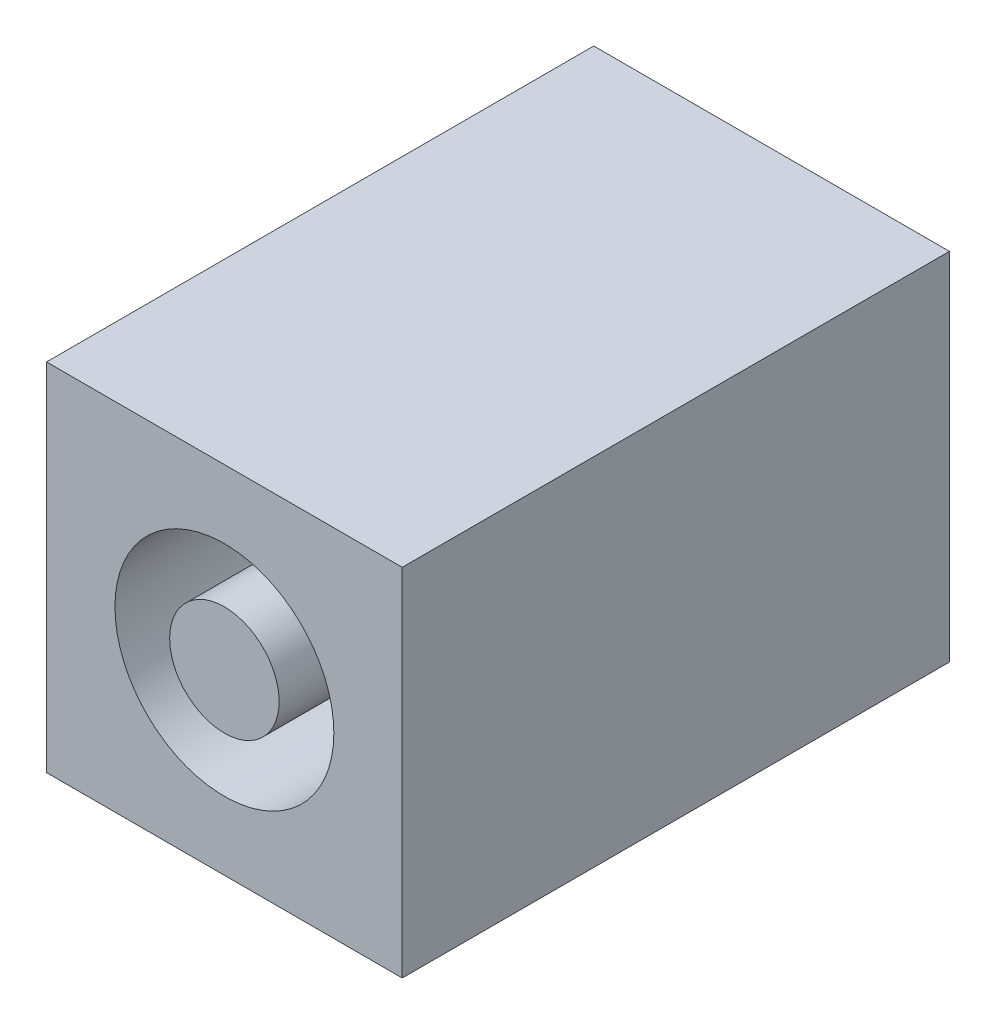
SolidWorks part; units mm, degrees
ref_plane "정면" through (0, 0, 0) normal (0, 0, 1) x (1, 0, 0)
ref_plane "윗면" through (0, 0, 0) normal (0, 1, 0) x (1, 0, 0)
ref_plane "우측면" through (0, 0, 0) normal (1, 0, 0) x (0, 0, -1)
ref_axis "기준축2" through (0, 0, 210) along (0, 0, -1)
ref_axis "기준축4" through (0, 55, 0) along (0, -1, 0)
sketch "스케치1" plane through (0, 0, 0) normal (0, 0, 1) x (1, 0, 0)
  line L1 (-65, 65) -> (65, 65)
  line L2 (-65, 65) -> (-65, -65)
  line L3 (-65, -65) -> (65, -65)
  line L4 (65, 65) -> (65, -65)
  circle A0 centre (0, 0) radius 35 construction
  circle A1 centre (0, 0) radius 25 construction
  circle A2 centre (0, 0) radius 40
  circle A3 centre (0, 0) radius 20
  point P11 (65, 0)
  point P14 (0, 65)
  dimension "D1" = 70
  dimension "D2" = 10
  dimension "D5" = 5
  dimension "D6" = 5
  dimension "D3" = 130
  dimension "D4" = 130
extrude "보스-돌출1" add sketch "스케치1" along normal blind 200 contours L4 L1 L2 L3 A2 | A3 region at (0, 63.1615, 0) region at (0, 0, 0)
sketch "스케치2" plane through (0, 0, 0) normal (0, 0, -1) x (-1, 0, 0)
  line L1 (-65, 65) -> (65, 65)
  line L2 (-65, 65) -> (-65, -65)
  line L3 (-65, -65) -> (65, -65)
  line L4 (65, 65) -> (65, -65)
extrude "보스-돌출2" add sketch "스케치2" against normal blind 3
